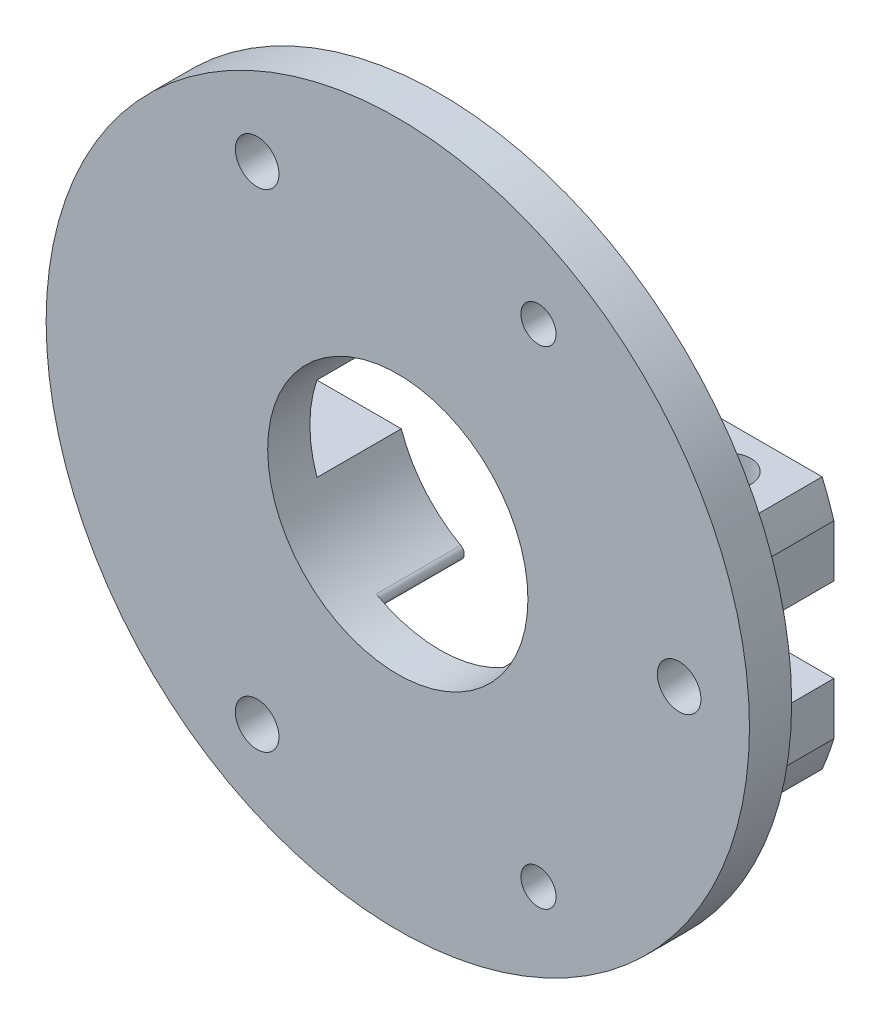
SolidWorks part; units mm, degrees
material "6061 合金"
ref_plane "前视基准面" through (0, 0, 0) normal (0, 0, 1) x (1, 0, 0)
ref_plane "上视基准面" through (0, 0, 0) normal (0, 1, 0) x (1, 0, 0)
ref_plane "右视基准面" through (0, 0, 0) normal (1, 0, 0) x (0, 0, -1)
sketch "草图1" plane through (0, 0, 0) normal (0, 0, 1) x (1, 0, 0)
  line L1 (-8.5, 18.1039) -> (8.5, 18.1039) construction
  line L2 (-8.5, 18.1039) -> (-8.5, -18.1039) construction
  line L3 (-8.5, -18.1039) -> (8.5, -18.1039) construction
  line L4 (8.5, 18.1039) -> (8.5, -18.1039) construction
  line L5 (-8.5, 18.1039) -> (8.5, -18.1039) construction
  line L6 (-8.5, -18.1039) -> (8.5, 18.1039) construction
  circle A0 centre (0, 0) radius 20 construction
  circle A1 centre (0, 0) radius 23
  circle A2 centre (0, 0) radius 9.25
  circle A3 centre (-8.5, -18.1039) radius 1.6 construction
  circle A4 centre (8.5, -18.1039) radius 1.6 construction
  circle A5 centre (8.5, 18.1039) radius 1.6 construction
  circle A6 centre (-8.5, 18.1039) radius 1.6 construction
  dimension "D1" = 40
  dimension "D2" = 18.5
  dimension "D3" = 46
  dimension "D5" = 3.2
  dimension "D4" = 17
extrude "凸台-拉伸1" add sketch "草图1" along normal blind 3
sketch "草图2" plane through (0, 0, 0) normal (0, 0, -1) x (-1, 0, 0)
  line L0 (-4.9258, -9) -> (-22, -9) construction
  line L1 (22, 9) -> (-22, 9)
  line L2 (22, 9) -> (22, -9)
  line L3 (22, -9) -> (-22, -9)
  line L4 (-22, 9) -> (-22, -9)
  line L5 (22, 9) -> (-22, -9) construction
  line L6 (22, -9) -> (-22, 9) construction
  line L7 (-17, -3) -> (22, -3) construction
  line L8 (-22, 3) -> (22, 3)
  line L9 (-22, 3) -> (-22, -3)
  line L10 (-22, -3) -> (22, -3)
  line L11 (22, 3) -> (22, -3)
  line L12 (22, -3) -> (22, 3) construction
  circle A0 centre (0, 0) radius 9
  point P0 (0, 0)
  circle M5 centre (0, 0) radius 23
  circle M6 centre (0, 0) radius 9.25
  dimension "D1" = 18
extrude "凸台-拉伸2" add sketch "草图2" along normal blind 6 contours L8 L1 M5 M6 | L4 L8 L1 M5 | L8 L1 M6 M5 | L8 L2 L1 M5 | L10 L3 L2 M5 | L10 L3 M6 M5 | L10 L3 M5 M6 | L10 L4 L3 M5 region at (-21.7294, 8.2581, 0) region at (-14.1264, 6.1686, 0) region at (21.7294, 8.2581, 0) region at (14.1264, 6.1686, 0) region at (-14.1264, -6.1686, 0) region at (-21.7294, -8.2581, 0) region at (21.7294, -8.2581, 0) region at (14.1264, -6.1686, 0)
sketch "草图3" plane through (0, -9, 0) normal (0, -1, 0) x (1, 0, 0)
  line L0 (2.136, 0) -> (21.166, 0) construction
  circle A4 centre (-17.5, -3) radius 1.6
  circle A5 centre (17.5, -3) radius 1.6
  dimension "D1" = 3.2
  dimension "D2" = 35
  dimension "D3" = 17.5
  dimension "D4" = 3
extrude "切除-拉伸1" cut sketch "草图3" against normal through all
fillet "圆角3" radius 0.5 4 edges at (2.136, -9, -3) (-2.136, -9, -3) (-2.136, 9, -3) (2.136, 9, -3)
sketch "草图4" plane through (0, 0, -6) normal (0, 0, -1) x (-1, 0, 0)
  circle A0 centre (0, 0) radius 23
  circle A1 centre (0, 0) radius 23 construction
  circle A2 centre (0, 0) radius 25
  dimension "D1" = 50
extrude "切除-拉伸2" cut sketch "草图4" against normal blind 10
sketch "草图5" plane through (0, 0, 0) normal (0, 0, 1) x (1, 0, 0)
  line L0 (-21.166, -9) -> (-4.7762, -9) construction
  line L1 (17.4356, 15) -> (-17.4356, 15) construction
  line L2 (17.4356, 15) -> (17.4356, -15) construction
  line L3 (17.4356, -15) -> (-17.4356, -15) construction
  line L4 (-17.4356, 15) -> (-17.4356, -15) construction
  line L5 (17.4356, 15) -> (-17.4356, -15) construction
  line L6 (17.4356, -15) -> (-17.4356, 15) construction
  line L7 (0, 25) -> (0, -25) construction
  line L8 (10, 21) -> (-10, 21) construction
  line L9 (10, 21) -> (10, -21) construction
  line L10 (10, -21) -> (-10, -21) construction
  line L11 (-10, 21) -> (-10, -21) construction
  line L12 (10, 21) -> (-10, -21) construction
  line L13 (10, -21) -> (-10, 21) construction
  circle A0 centre (0, 0) radius 25
  arc A1 (-21.166, -9) -> (21.166, -9) centre (0, 0) ccw construction
  circle A2 centre (-10, -21) radius 1.6 construction
  circle A3 centre (10, -21) radius 1.6 construction
  circle A4 centre (10, 21) radius 1.6 construction
  circle A5 centre (-10, 21) radius 1.6 construction
  circle A6 centre (0, 0) radius 9.25 construction
  circle A7 centre (0, 0) radius 9.25
  dimension "D1" = 50
  dimension "D5" = 3.2
  dimension "D2" = 6
  dimension "D3" = 20
  dimension "D4" = 42
extrude "凸台-拉伸3" add sketch "草图5" along normal blind 3
sketch "草图11" plane through (0, 0, 0) normal (0, 1, 0) x (1, 0, 0)
  line L0 (20, -8.0622) -> (20, 8.0622) construction
  line L1 (21.55, -3) -> (21.55, -1.45)
  line L2 (-25, -3) -> (25, -3) construction
  line L3 (21.55, -1.45) -> (23, 0)
  line L4 (25, 0) -> (-25, 0) construction
  line L5 (23, 0) -> (20, 0)
  line L6 (20, 0) -> (20, -3)
  line L7 (20, -3) -> (21.55, -3)
  line L8 (22, 0) -> (21.166, 0) construction
  dimension "D1" = 20
  dimension "D2" = 45
  dimension "D3" = 3.1
  dimension "D4" = 6
revolve "切除-旋转1" cut sketch "草图11" angle 360 about L0
pattern_circular "阵列(圆周)1" count 3 over 360 about axis through (0, 0, 0) along (0, 0, 1) of "切除-旋转1"
sketch "草图12" plane through (0, 0, 0) normal (0, 0, -1) x (-1, 0, 0)
  circle A0 centre (10, 17.3205) radius 3 construction
  circle A1 centre (10, 17.3205) radius 1.55 construction
  circle A2 centre (10, -17.3205) radius 3 construction
  circle A3 centre (10, -17.3205) radius 1.55 construction
  circle A4 centre (10, 17.3205) radius 3
  circle A5 centre (10, 17.3205) radius 1.55
  circle A6 centre (10, -17.3205) radius 3
  circle A7 centre (10, -17.3205) radius 1.55
extrude "凸台-拉伸4" add sketch "草图12" against normal blind 2
sketch "草图13" plane through (0, 0, 0) normal (0, 0, -1) x (-1, 0, 0)
  line L1 (-10, 17.3205) -> (10, 17.3205) construction
  line L2 (-10, 17.3205) -> (-10, -17.3205) construction
  line L3 (-10, -17.3205) -> (10, -17.3205) construction
  line L4 (10, 17.3205) -> (10, -17.3205) construction
  line L5 (-10, 17.3205) -> (10, -17.3205) construction
  line L6 (-10, -17.3205) -> (10, 17.3205) construction
  circle A0 centre (-10, -17.3205) radius 1.55
  circle A1 centre (-10, 17.3205) radius 1.55
  circle A2 centre (10, -17.3205) radius 1.55 construction
  point P0 (0, 0)
hole_wizard "M3 螺纹孔1" positions "草图14" profile "草图15" tap size "M3" standard "GB"
sketch "草图14" plane through (0, 0, 0) normal (0, 0, -1) x (-1, 0, 0)
  point P0 (-10, 17.3205)
  point P3 (-10, -17.3205)
sketch "草图15" plane through (10, 17.3205, 0) normal (1, 0, 0) x (0, 1, 0)
  line L0 (0, 0) -> (0, 13.2511)
  line L1 (0, 13.2511) -> (1.25, 12.5)
  line L2 (1.25, 12.5) -> (1.25, 0)
  line L5 (1.25, 0) -> (0, 0)
  line L10 (0, 13.2511) -> (-1.25, 12.5) construction
  line L11 (0, -6.35) -> (0, 107.95) construction
  dimension "螺纹孔钻头直径" = 2.5
  dimension "螺纹孔钻头深度" = 12.5
  dimension "导头角度" = 118
cosmetic thread "孔螺蚊线1" parameters "D1"=10, "D2"=3
cosmetic thread "孔螺蚊线2" parameters "D1"=10, "D2"=3
sketch "草图16" plane through (0, 0, 0) normal (0, 0, -1) x (-1, 0, 0)
  circle A0 centre (-20, 0) radius 1.55 construction
  circle A1 centre (-20, 0) radius 1.55
  circle A2 centre (-20, 0) radius 3
  arc A3 (-20, -3) -> (-20, 3) centre (-20, 0) ccw construction
extrude "凸台-拉伸5" add sketch "草图16" against normal blind 3
